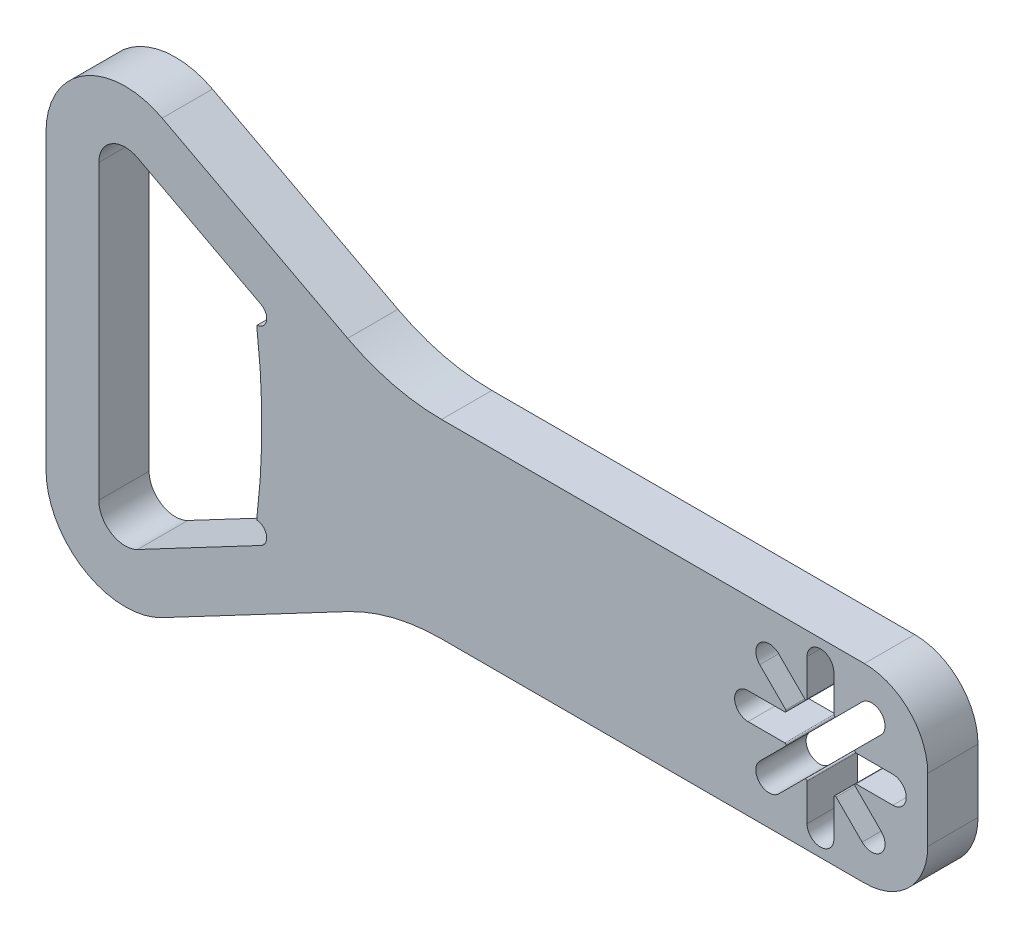
SolidWorks part; units mm, degrees
ref_plane "Front Plane" through (0, 0, 0) normal (0, 0, 1) x (1, 0, 0)
ref_plane "Top Plane" through (0, 0, 0) normal (0, 1, 0) x (1, 0, 0)
ref_plane "Right Plane" through (0, 0, 0) normal (1, 0, 0) x (0, 0, -1)
sketch "Model" plane through (0, 0, 0) normal (0, 0, 1) x (1, 0, 0)
  line L0 (93.451, 245.0307) -> (75.8892, 254.3082)
  line L1 (64.8859, 247.6767) -> (64.8859, 219.9729)
  line L2 (75.8892, 213.3414) -> (93.451, 222.6188)
  line L3 (102.3493, 224.8248) -> (142.3859, 224.8248)
  line L4 (73.5537, 217.7624) -> (85.2574, 223.9452)
  line L5 (69.8859, 247.6767) -> (69.8859, 219.9729)
  line L6 (85.2574, 243.7044) -> (73.5537, 249.8872)
  line L7 (84.8859, 225.8248) -> (84.8859, 226.3248)
  line L8 (84.8859, 241.3248) -> (84.8859, 241.8248)
  line L9 (142.3859, 242.8248) -> (102.3493, 242.8248)
  line L10 (148.3859, 230.8248) -> (148.3859, 236.8248)
  arc A0 (93.451, 245.0307) -> (102.3493, 242.8248) centre (102.3493, 261.8748) ccw
  arc A1 (75.8892, 254.3082) -> (64.8859, 247.6767) centre (72.3859, 247.6767) ccw
  arc A2 (64.8859, 219.9729) -> (75.8892, 213.3414) centre (72.3859, 219.9729) ccw
  arc A3 (102.3493, 224.8248) -> (93.451, 222.6188) centre (102.3493, 205.7748) ccw
  arc A4 (69.8859, 219.9729) -> (73.5537, 217.7624) centre (72.3859, 219.9729) ccw
  arc A5 (73.5537, 249.8872) -> (69.8859, 247.6767) centre (72.3859, 247.6767) ccw
  arc A6 (85.2574, 223.9452) -> (85.7424, 225.1352) centre (84.7903, 224.8294) ccw
  arc A7 (85.7424, 242.5144) -> (85.2574, 243.7044) centre (84.7903, 242.8202) ccw
  arc A9 (85.7424, 225.1352) -> (84.8859, 225.8248) centre (84.7903, 224.8294) ccw
  arc A10 (84.8859, 226.3248) -> (84.8859, 241.3248) centre (21.8304, 233.8248) ccw
  arc A11 (84.8859, 241.8248) -> (85.7424, 242.5144) centre (84.7903, 242.8202) ccw
  arc A12 (148.3859, 236.8248) -> (142.3859, 242.8248) centre (142.3859, 236.8248) ccw
  arc A13 (142.3859, 224.8248) -> (148.3859, 230.8248) centre (142.3859, 230.8248) ccw
extrude "Boss-Extrude1" add sketch "Model" along normal blind 4.7625
sketch "Sketch2" plane through (0, 0, 4.7625) normal (0, 0, 1) x (1, 0, 0)
  line L8 (136.9559, 226.9668) -> (136.9559, 230.7587)
  line L9 (139.4959, 226.9668) -> (139.4959, 230.7587)
  line L11 (132.4785, 229.8735) -> (135.1599, 232.5548)
  line L12 (134.2746, 228.0774) -> (136.9559, 230.7587)
  line L14 (131.3679, 235.0948) -> (135.1599, 235.0948)
  line L15 (131.3679, 232.5548) -> (135.1599, 232.5548)
  line L17 (134.2746, 239.5721) -> (136.9559, 236.8908)
  line L18 (132.4785, 237.7761) -> (135.1599, 235.0948)
  line L19 (136.9559, 236.8908) -> (136.9559, 240.6828)
  line L21 (139.4959, 236.8908) -> (142.1772, 239.5721)
  line L22 (139.4959, 236.8908) -> (139.4959, 240.6828)
  line L23 (141.292, 235.0948) -> (145.0839, 235.0948)
  line L24 (141.292, 235.0948) -> (143.9733, 237.7761)
  line L25 (141.292, 232.5548) -> (143.9733, 229.8735)
  line L26 (141.292, 232.5548) -> (145.0839, 232.5548)
  line L28 (139.4959, 230.7587) -> (142.1772, 228.0774)
  arc A0 (136.9559, 226.9668) -> (139.4959, 226.9668) centre (138.2259, 226.9668) ccw
  arc A1 (139.4959, 240.6828) -> (136.9559, 240.6828) centre (138.2259, 240.6828) ccw
  arc A2 (132.4785, 229.8735) -> (134.2746, 228.0774) centre (133.3766, 228.9754) ccw
  arc A3 (143.9733, 237.7761) -> (142.1772, 239.5721) centre (143.0752, 238.6741) ccw
  arc A4 (131.3679, 235.0948) -> (131.3679, 232.5548) centre (131.3679, 233.8248) ccw
  arc A5 (145.0839, 232.5548) -> (145.0839, 235.0948) centre (145.0839, 233.8248) ccw
  arc A6 (134.2746, 239.5721) -> (132.4785, 237.7761) centre (133.3766, 238.6741) ccw
  arc A7 (142.1772, 228.0774) -> (143.9733, 229.8735) centre (143.0752, 228.9754) ccw
  dimension "D4" = 2.54
  dimension "D5" = 2.54
  dimension "D6" = 2.54
  dimension "D7" = 2.54
extrude "Cut-Extrude1" cut sketch "Sketch2" against normal through all
fillet "Fillet1" radius 0.127 8 edges at (136.9559, 230.7587, 2.3813) (139.4959, 230.7587, 2.3813) (141.292, 235.0948, 2.3813) (141.292, 232.5548, 2.3813) (135.1599, 232.5548, 2.3813) (135.1599, 235.0948, 2.3813) (136.9559, 236.8908, 2.3813) (139.4959, 236.8908, 2.3813)
